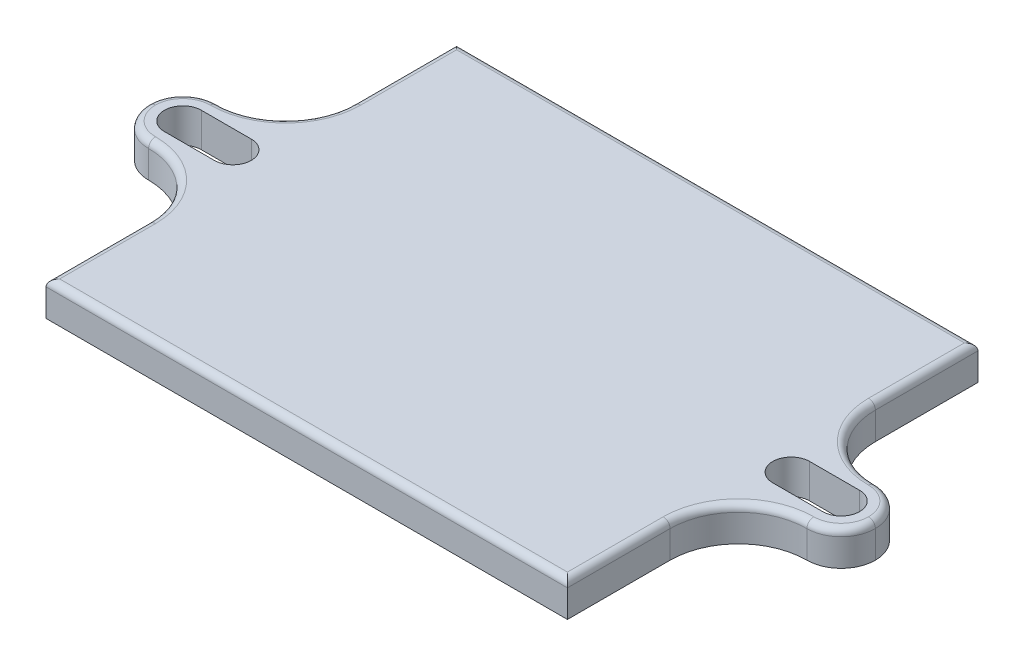
SolidWorks part; units mm, degrees
ref_plane "Front Plane" through (0, 0, 0) normal (0, 0, 1) x (1, 0, 0)
ref_plane "Top Plane" through (0, 0, 0) normal (0, 1, 0) x (1, 0, 0)
ref_plane "Right Plane" through (0, 0, 0) normal (1, 0, 0) x (0, 0, -1)
sketch "Sketch1" plane through (0, 0, 0) normal (0, 1, 0) x (1, 0, 0)
  line L0 (-38.1, 30) -> (38.1, -30) construction
  line L1 (-38.1, 30) -> (38.1, 30)
  line L2 (-38.1, 30) -> (-38.1, -30)
  line L3 (-38.1, -30) -> (38.1, -30)
  line L4 (38.1, 30) -> (38.1, -30)
  dimension "D1" = 76.2
  dimension "D2" = 60
extrude "Boss-Extrude1" add sketch "Sketch1" along normal mid plane 5
sketch "Sketch2" plane through (0, 0, 0) normal (0, 1, 0) x (1, 0, 0)
  line L0 (-38.1, 30) -> (-38.1, -30) construction
  line L1 (-38.1, 5) -> (-53.1, 5)
  line L2 (-38.1, 5) -> (-38.1, -5)
  line L3 (-38.1, -5) -> (-53.1, -5)
  line L4 (-53.1, 5) -> (-53.1, -5)
  point P6 (-53.1, 0)
  dimension "D1" = 10
  dimension "D2" = 15
extrude "Boss-Extrude2" add sketch "Sketch2" along normal mid plane 5
sketch "Sketch3" plane through (0, 2.5, 0) normal (0, 1, 0) x (1, 0, 0)
  line L0 (-53.1, 5) -> (-53.1, -5) construction
  line L1 (-48.1, 2.7) -> (-40.8, 2.7)
  line L3 (-48.1, -2.7) -> (-40.8, -2.7)
  line L5 (-38.1, 30) -> (-38.1, 5) construction
  arc A0 (-40.8, 2.7) -> (-40.8, -2.7) centre (-40.8, 0) cw
  arc A1 (-48.1, 2.7) -> (-48.1, -2.7) centre (-48.1, 0) ccw
  dimension "D1" = 5.4
  dimension "D2" = 5
extrude "Cut-Extrude1" cut sketch "Sketch3" against normal blind 10
mirror "Mirror4" about plane through (0, 0, 0) normal (1, 0, 0) of "Cut-Extrude1", "Boss-Extrude2"
fillet "Fillet1" radius 10 4 edges at (-38.1, 0, -5) (-38.1, 0, 5) (38.1, 0, -5) (38.1, 0, 5)
fillet "Fillet2" radius 5 4 edges at (-53.1, 0, -5) (-53.1, 0, 5) (53.1, 0, -5) (53.1, 0, 5)
fillet "Fillet3" radius 1 14 edges at (38.1, 2.5, 22.5) (41.0289, 2.5, 7.9289) (51.6355, 2.5, 3.5355) (51.6355, 2.5, -3.5355) (41.0289, 2.5, -7.9289) (-38.1, 2.5, -22.5) (-41.0289, 2.5, -7.9289) (-51.6355, 2.5, -3.5355) (-51.6355, 2.5, 3.5355) (-41.0289, 2.5, 7.9289) (38.1, 2.5, -22.5) (0, 2.5, -30) (-38.1, 2.5, 22.5) (0, 2.5, 30)
